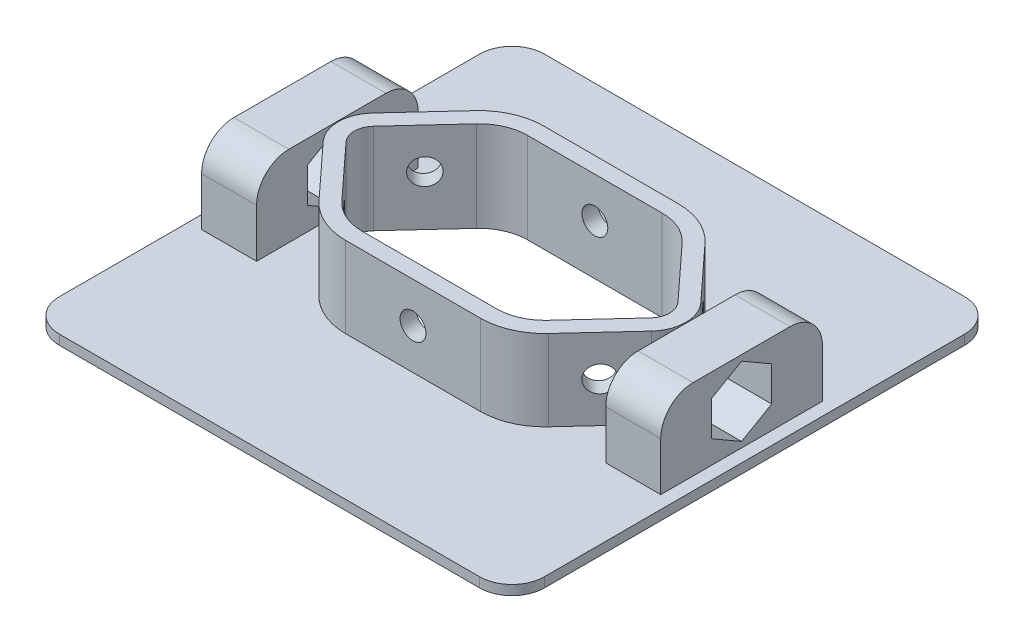
SolidWorks part; units mm, degrees
ref_plane "Front Plane" through (0, 0, 0) normal (0, 0, 1) x (1, 0, 0)
ref_plane "Top Plane" through (0, 0, 0) normal (0, 1, 0) x (1, 0, 0)
ref_plane "Right Plane" through (0, 0, 0) normal (1, 0, 0) x (0, 0, -1)
sketch "Sketch1" plane through (0, 0, 0) normal (0, 1, 0) x (1, 0, 0)
  line L1 (-30, -30) -> (30, -30)
  line L2 (-30, -30) -> (-30, 30)
  line L3 (-30, 30) -> (30, 30)
  line L4 (30, -30) -> (30, 30)
  line L5 (-30, -30) -> (30, 30) construction
  line L6 (-30, 30) -> (30, -30) construction
  point P0 (0, 0)
  dimension "D1" = 60
  dimension "D2" = 60
extrude "Boss-Extrude1" add sketch "Sketch1" along normal blind 1.2
fillet "Fillet1" radius 4 4 edges at (-30, 0.6, -30) (-30, 0.6, 30) (30, 0.6, -30) (30, 0.6, 30)
sketch "Sketch3" plane through (0, 1.2, 0) normal (0, 1, 0) x (1, 0, 0)
  line L4 (-28.4, -10) -> (-21.6, -10)
  line L5 (-28.4, -10) -> (-28.4, 10)
  line L6 (-28.4, 10) -> (-21.6, 10)
  line L7 (-21.6, -10) -> (-21.6, 10)
  line L8 (30, 0) -> (28.4, 0)
  line L9 (30, -26) -> (30, 26) construction
  line L11 (28.4, 10) -> (21.6, 10)
  line L12 (21.6, -10) -> (21.6, 10)
  line L13 (28.4, -10) -> (21.6, -10)
  line L14 (28.4, -10) -> (28.4, 10)
  dimension "D1" = 20
  dimension "D2" = 6.8
  dimension "D3" = 6.8
extrude "Boss-Extrude3" add sketch "Sketch3" along normal blind 10 contours L4 L7 L6 L5 | L13 L14 L11 L12 region at (-25, 1.2, 0) region at (25, 1.2, 0)
fillet "Fillet2" radius 4 4 edges at (25, 11.2, -10) (25, 11.2, 10) (-25, 11.2, 10) (-25, 11.2, -10)
sketch "Sketch4" plane through (-28.4, 0, 0) normal (-1, 0, 0) x (0, 0, 1)
  line L0 (0, 11.2) -> (0, 1.2)
  line L1 (6, 11.2) -> (-6, 11.2) construction
  line L2 (10, 1.2) -> (-10, 1.2) construction
  line L4 (0, 10.5) -> (-3.7239, 8.35)
  line L5 (-3.7239, 8.35) -> (-3.7239, 4.05)
  line L6 (-3.7239, 4.05) -> (0, 1.9)
  line L7 (0, 1.9) -> (3.7239, 4.05)
  line L8 (3.7239, 4.05) -> (3.7239, 8.35)
  line L9 (3.7239, 8.35) -> (0, 10.5)
  circle A0 centre (0, 6.2) radius 4.3 construction
extrude "Cut-Extrude1" cut sketch "Sketch4" against normal blind 100 contours L5 L6 L0 L4 | L8 L9 L0 L7 region at (-28.4, 6.2, 1.6551) region at (-28.4, 6.2, -1.6551)
sketch "Sketch5" plane through (0, 1.2, 0) normal (0, 1, 0) x (1, 0, 0)
  line L0 (18.8382, 1.6944) -> (12.7344, 8.3165)
  line L1 (8.3226, 10.25) -> (-8.3226, 10.25)
  line L2 (-12.7344, 8.3165) -> (-18.8382, 1.6944)
  line L3 (-12.7344, -8.3165) -> (-18.8382, -1.6944)
  line L4 (8.3226, -10.25) -> (-8.3226, -10.25)
  line L5 (18.8382, -1.6944) -> (12.7344, -8.3165)
  line L6 (20.3088, 3.0499) -> (14.205, 9.672)
  line L7 (8.3226, 12.25) -> (-8.3226, 12.25)
  line L8 (-14.205, 9.672) -> (-20.3088, 3.0499)
  line L9 (-14.205, -9.672) -> (-20.3088, -3.0499)
  line L10 (8.3226, -12.25) -> (-8.3226, -12.25)
  line L11 (20.3088, -3.0499) -> (14.205, -9.672)
  arc A0 (12.7344, 8.3165) -> (8.3226, 10.25) centre (8.3226, 4.25) ccw
  arc A1 (-8.3226, 10.25) -> (-12.7344, 8.3165) centre (-8.3226, 4.25) ccw
  arc A2 (-18.8382, 1.6944) -> (-18.8382, -1.6944) centre (-17, 0) ccw
  arc A3 (-8.3226, -10.25) -> (-12.7344, -8.3165) centre (-8.3226, -4.25) cw
  arc A4 (12.7344, -8.3165) -> (8.3226, -10.25) centre (8.3226, -4.25) cw
  arc A5 (18.8382, 1.6944) -> (18.8382, -1.6944) centre (17, 0) cw
  arc A6 (14.205, 9.672) -> (8.3226, 12.25) centre (8.3226, 4.25) ccw
  arc A7 (-8.3226, 12.25) -> (-14.205, 9.672) centre (-8.3226, 4.25) ccw
  arc A8 (-20.3088, 3.0499) -> (-20.3088, -3.0499) centre (-17, 0) ccw
  arc A9 (-8.3226, -12.25) -> (-14.205, -9.672) centre (-8.3226, -4.25) cw
  arc A10 (14.205, -9.672) -> (8.3226, -12.25) centre (8.3226, -4.25) cw
  arc A11 (20.3088, 3.0499) -> (20.3088, -3.0499) centre (17, 0) cw
extrude "Cut-Extrude2" cut sketch "Sketch5" against normal through all contours L1 A1 L2 A2 L3 A3 L4 A4 L5 A5 L0 A0
extrude "Boss-Extrude4" add sketch "Sketch5<3>" along normal blind 10
sketch "Sketch5<3>" plane through (0, 1.2, 0) normal (0, 1, 0) x (1, 0, 0) same geometry as "Sketch5"
sketch "Sketch6" plane through (0, 0, 12.25) normal (0, 0, 1) x (1, 0, 0)
  line L0 (0, 11.2) -> (0, 1.2) construction
  line L1 (-8.3226, 11.2) -> (8.3226, 11.2) construction
  line L2 (-8.3226, 1.2) -> (8.3226, 1.2) construction
  circle A0 centre (0, 6.2) radius 1.6
extrude "Cut-Extrude4" cut sketch "Sketch6" against normal up to surface (24.5 mm away) up to face at (0, 6.2, -12.25)
sketch "Sketch7" plane through (-12.5, 0, 11.5217) normal (-0.7353, 0, 0.6777) x (0.6777, 0, 0.7353)
  line L0 (-7.0187, 11.2) -> (-7.0187, 1.2) construction
  line L1 (-11.5217, 11.2) -> (-2.5156, 11.2) construction
  line L2 (-11.5217, 1.2) -> (-2.5156, 1.2) construction
  circle A0 centre (-7.0187, 6.2) radius 1.6
extrude "Cut-Extrude5" cut sketch "Sketch7" against normal up to next
sketch "Sketch8" plane through (12.5, 0, 11.5217) normal (0.7353, 0, 0.6777) x (0.6777, 0, -0.7353)
  line L0 (7.0187, 11.2) -> (7.0187, 1.2) construction
  line L1 (2.5156, 11.2) -> (11.5217, 11.2) construction
  line L2 (2.5156, 1.2) -> (11.5217, 1.2) construction
  circle A0 centre (7.0187, 6.2) radius 1.6
extrude "Cut-Extrude6" cut sketch "Sketch8" against normal up to next
sketch "Sketch9" plane through (-12.5, 0, -11.5217) normal (-0.7353, 0, -0.6777) x (-0.6777, 0, 0.7353)
  line L0 (7.0187, 11.2) -> (7.0187, 1.2) construction
  line L1 (2.5156, 11.2) -> (11.5217, 11.2) construction
  line L2 (2.5156, 1.2) -> (11.5217, 1.2) construction
  circle A0 centre (7.0187, 6.2) radius 1.6
extrude "Cut-Extrude7" cut sketch "Sketch9" against normal up to next
sketch "Sketch10" plane through (12.5, 0, -11.5217) normal (0.7353, 0, -0.6777) x (-0.6777, 0, -0.7353)
  line L0 (-7.0187, 11.2) -> (-7.0187, 1.2) construction
  line L1 (-11.5217, 11.2) -> (-2.5156, 11.2) construction
  line L2 (-11.5217, 1.2) -> (-2.5156, 1.2) construction
  circle A0 centre (-7.0187, 6.2) radius 1.6
extrude "Cut-Extrude8" cut sketch "Sketch10" against normal up to next
